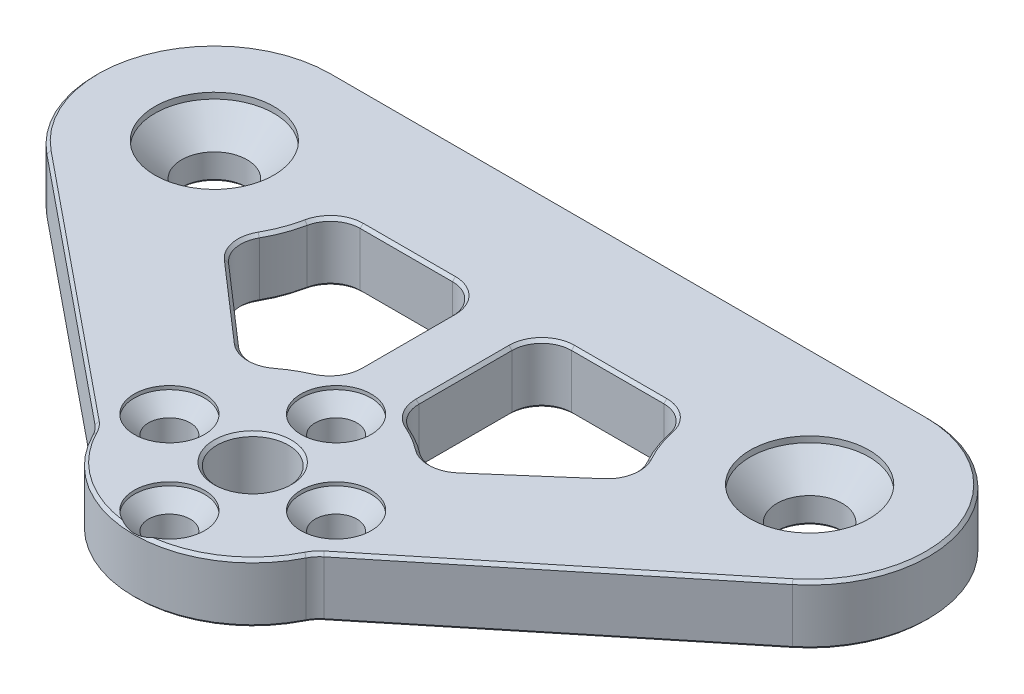
SolidWorks part; units mm, degrees
ref_plane "Front Plane" through (0, 0, 0) normal (0, 0, 1) x (1, 0, 0)
ref_plane "Top Plane" through (0, 0, 0) normal (0, 1, 0) x (1, 0, 0)
ref_plane "Right Plane" through (0, 0, 0) normal (1, 0, 0) x (0, 0, -1)
sketch "Sketch1" plane through (0, 0, 0) normal (0, 1, 0) x (1, 0, 0)
  line L0 (-16.5071, 0) -> (18.0457, 0) construction
  line L3 (0, 18.6761) -> (0, -19.8554) construction
  line L4 (-20.1562, 9.6) -> (19.941, 9.6) construction
  line L6 (-12.35, 0) -> (-12.35, 9.6) construction
  line L8 (-11.6844, 9.7174) -> (19.4918, 15.2146) construction
  line L10 (-10.4796, 11.7776) -> (18.3765, 11.7776) construction
  line L11 (-27.4571, 31.7776) -> (13.2195, 31.7776) construction
  line L12 (0, 31.7776) -> (0, 11.7776) construction
  line L13 (-6.75, 21.7776) -> (8.584, 21.7776) construction
  line L14 (-31.3116, 14.0211) -> (-9.1652, -4)
  line L15 (31.3116, 14.0211) -> (9.1652, -4)
  line L16 (-25, 31.7776) -> (25, 31.7776)
  circle A2 centre (0, 0) radius 7 construction
  circle A3 centre (0, 7) radius 1.75
  circle A4 centre (7, 0) radius 1.75
  circle A5 centre (0, -7) radius 1.75
  circle A6 centre (-7, 0) radius 1.75
  circle A7 centre (0, 0) radius 3
  arc A8 (-9.1652, -4) -> (9.1652, -4) centre (0, 0) ccw
  circle A9 centre (-25, 21.7776) radius 2.75
  arc A10 (-25, 31.7776) -> (-31.3116, 14.0211) centre (-25, 21.7776) ccw
  arc A11 (25, 31.7776) -> (31.3116, 14.0211) centre (25, 21.7776) cw
  circle A12 centre (25, 21.7776) radius 2.75
  point P1 (0, 0)
  point P4 (-9.6682, -2.5548)
  point P22 (0, 11.7776)
  point P31 (0, 21.7776)
  dimension "D1" = 20
  dimension "D3" = 14
  dimension "D4" = 3.5
  dimension "D5" = 6
  dimension "D6" = 12.35
  dimension "D8" = 20
  dimension "D9" = 5.5
  dimension "D2" = 9.6
  dimension "D7" = 10
  dimension "D10" = 50
  dimension "D11" = 4
extrude "Boss-Extrude1" add sketch "Sketch1" along normal blind 5
hole_wizard "CSK for M3 Flat Head Machine Screw2" positions "Sketch2" profile "Sketch3" countersink size "M3" standard "ANSI Metric" end condition through all
sketch "Sketch2" plane through (0, 5, 0) normal (0, 1, 0) x (1, 0, 0)
  point P0 (0, 7)
  point P3 (7, 0)
  point P6 (0, -7)
  point P9 (-7, 0)
sketch "Sketch3" plane through (0, 5, -7) normal (1, 0, 0) x (0, 0, 1)
  line L0 (0, 0) -> (0, 5)
  line L1 (0, 5) -> (1.75, 5)
  line L2 (1.75, 5) -> (1.75, 1.5)
  line L3 (1.75, 1.5) -> (2.95, 0.3)
  line L4 (2.95, 0.3) -> (2.95, 0)
  line L6 (2.95, 0) -> (0, 0)
  line L7 (-1.75, 1.5) -> (-2.95, 0.3) construction
  line L11 (0, -6.35) -> (0, 107.95) construction
  dimension "Thru Hole Dia." = 3.5
  dimension "Thru Hole Depth" = 5
  dimension "C'Sink Dia." = 5.9
  dimension "C'Sink Angle" = 90
  dimension "Head Clearance" = 0.3
hole_wizard "CSK for M5 Flat Head Machine Screw1" positions "Sketch4" profile "Sketch5" countersink size "M5" standard "ANSI Metric" end condition through all
sketch "Sketch4" plane through (0, 5, 0) normal (0, 1, 0) x (1, 0, 0)
  point P0 (-25, 21.7776)
  point P3 (25, 21.7776)
sketch "Sketch5" plane through (-25, 5, -21.7776) normal (1, 0, 0) x (0, 0, 1)
  line L0 (0, 0) -> (0, 5)
  line L1 (0, 5) -> (2.75, 5)
  line L2 (2.75, 5) -> (2.75, 2.75)
  line L3 (2.75, 2.75) -> (5, 0.5)
  line L4 (5, 0.5) -> (5, 0)
  line L6 (5, 0) -> (0, 0)
  line L7 (-2.75, 2.75) -> (-5, 0.5) construction
  line L11 (0, -6.35) -> (0, 107.95) construction
  dimension "Thru Hole Dia." = 5.5
  dimension "Thru Hole Depth" = 5
  dimension "C'Sink Dia." = 10
  dimension "C'Sink Angle" = 90
  dimension "Head Clearance" = 0.5
sketch "Sketch6" plane through (0, 5, 0) normal (0, 1, 0) x (1, 0, 0)
  line L0 (-25, 21.7776) -> (25, 21.7776)
  line L1 (25, 21.7776) -> (0, 0)
  line L2 (0, 0) -> (-25, 21.7776)
  line L3 (0, 0) -> (0, 21.7776) construction
  line L4 (2.5, 0) -> (2.5, 21.7776)
  line L5 (-2.5, 0) -> (-2.5, 21.7776)
  circle A0 centre (0, 0) radius 10
  arc A1 (-9.1652, -4) -> (9.1652, -4) centre (0, 0) ccw construction
  circle A2 centre (-25, 21.7776) radius 10
  arc A3 (-25, 31.7776) -> (-31.3116, 14.0211) centre (-25, 21.7776) ccw construction
  circle A4 centre (25, 21.7776) radius 10
  dimension "D1" = 2.5
  dimension "D2" = 2.5
extrude "Cut-Extrude1" cut sketch "Sketch6" against normal up to next contours A2 L2 A0 L5 L0 | L1 A4 L0 L4 A0
fillet "Fillet1" radius 2.5 12 edges at (15, 2.5, -21.7776) (17.4597, 2.5, -15.2092) (7.5403, 2.5, -6.5684) (2.5, 2.5, -9.6825) (2.5, 2.5, -21.7776) (-2.5, 2.5, -21.7776) (-2.5, 2.5, -9.6825) (-7.5403, 2.5, -6.5684) (-17.4597, 2.5, -15.2092) (-15, 2.5, -21.7776) (9.1652, 2.5, 4) (-9.1652, 2.5, 4)
chamfer "Chamfer1" distance 0.25 angle 45 64 edges at (25, 0, -24.5276) (-25, 0, -19.0276) (-7, 0, 1.75) (0, 0, 8.75) (7, 0, 1.75) (0, 0, -5.25) (-20.4599, 0, -5.1908) (0, 0, 10) (20.4599, 0, -5.1908) (34.4224, 0, -25.1269) (0, 0, -31.7776) (-34.4224, 0, -25.1269) (0, 0, 3) (0, 5, 3) (20.4599, 5, -5.1908) (-20.4599, 5, -5.1908) (34.4224, 5, -25.1269) (-34.4224, 5, -25.1269) (0, 5, -31.7776) (2.9083, 0, -10.0871) (2.5, 0, -15.367) (3.2322, 0, -21.0454) (8.8763, 0, -21.7776) (14.3337, 0, -21.2141) (15.6351, 0, -18.2707) (16.5871, 0, -15.1965) (12.5, 0, -10.8888) (7.6726, 0, -7.431) (5.074, 0, -8.6171) (-3.2322, 0, -21.0454) (-2.5, 0, -15.367) (-2.9083, 0, -10.0871) (-5.074, 0, -8.6171) (-7.6726, 0, -7.431) (-12.5, 0, -10.8888) (-16.5871, 0, -15.1965) (-15.6351, 0, -18.2707) (-14.3337, 0, -21.2141) (-8.8763, 0, -21.7776) (14.3337, 5, -21.2141) (15.6351, 5, -18.2707) (8.8763, 5, -21.7776) (16.5871, 5, -15.1965) (3.2322, 5, -21.0454) (12.5, 5, -10.8888) (2.5, 5, -15.367) (7.6726, 5, -7.431) (2.9083, 5, -10.0871) (5.074, 5, -8.6171) (-3.2322, 5, -21.0454) (-2.5, 5, -15.367) (-8.8763, 5, -21.7776) (-2.9083, 5, -10.0871) (-14.3337, 5, -21.2141) (-5.074, 5, -8.6171) (-15.6351, 5, -18.2707) (-7.6726, 5, -7.431) (-16.5871, 5, -15.1965) (-12.5, 5, -10.8888) (0, 5, 10) (-9.2346, 0, 4.016) (9.2346, 0, 4.016) (9.2346, 5, 4.016) (-9.2346, 5, 4.016)
